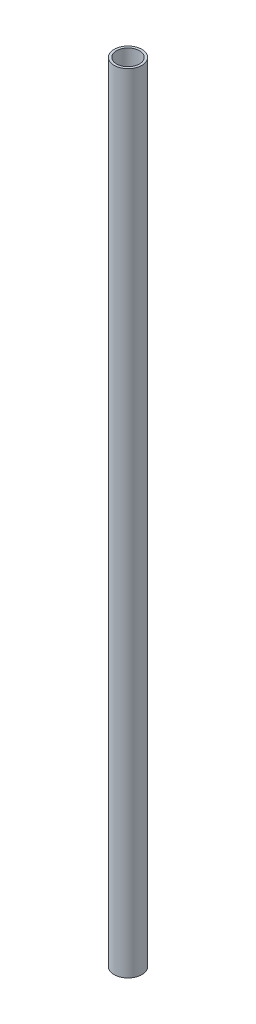
SolidWorks part; units mm, degrees
material "Plain Carbon Steel"
ref_plane "Front Plane" through (0, 0, 0) normal (0, 0, 1) x (1, 0, 0)
ref_plane "Top Plane" through (0, 0, 0) normal (0, 1, 0) x (1, 0, 0)
ref_plane "Right Plane" through (0, 0, 0) normal (1, 0, 0) x (0, 0, -1)
sketch "Sketch1" plane through (0, 0, 0) normal (0, 1, 0) x (1, 0, 0)
  circle A0 centre (0, 0) radius 17.4625
  circle A1 centre (0, 0) radius 14.4145
  dimension "D1" = 34.925
  dimension "D2" = 28.829
extrude "Boss-Extrude1" add sketch "Sketch1" along normal blind 989.9
